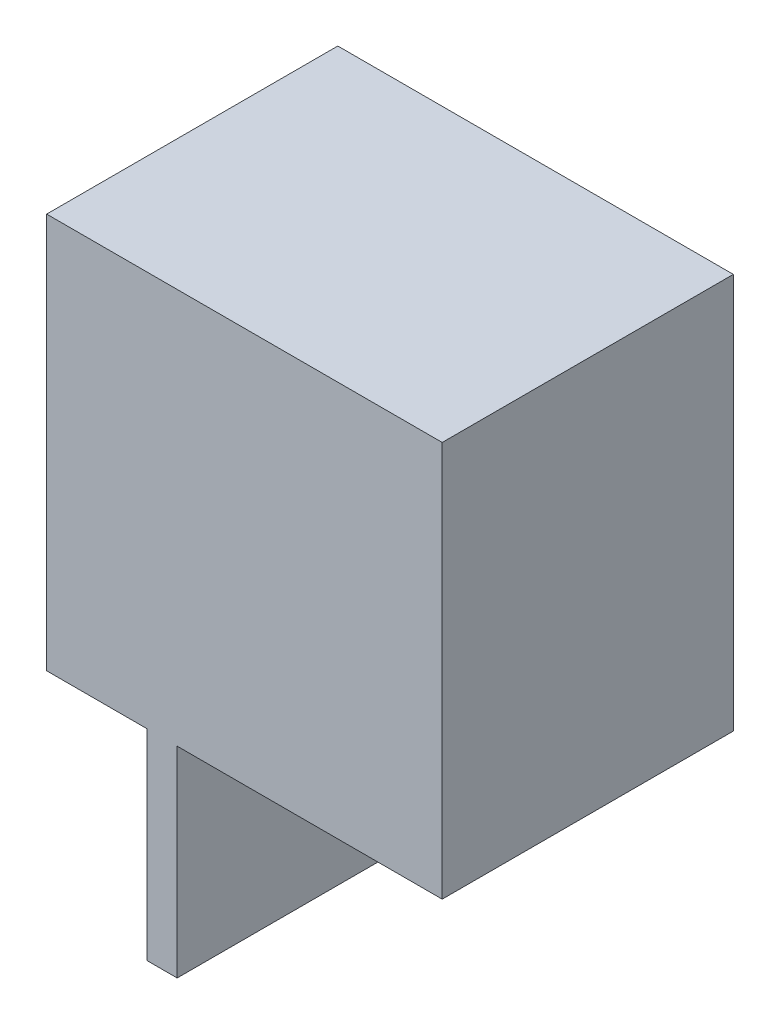
SolidWorks part; units mm, degrees
ref_plane "Front Plane" through (0, 0, 0) normal (0, 0, 1) x (1, 0, 0)
ref_plane "Top Plane" through (0, 0, 0) normal (0, 1, 0) x (1, 0, 0)
ref_plane "Right Plane" through (0, 0, 0) normal (1, 0, 0) x (0, 0, -1)
sketch "Sketch2" plane through (0, 0, 0) normal (0, 0, 1) x (1, 0, 0)
  line L1 (0, 0) -> (42.418, 0)
  line L2 (0, 0) -> (0, 42.418)
  line L3 (0, 42.418) -> (42.418, 42.418)
  line L4 (42.418, 0) -> (42.418, 42.418)
  line L5 (-3.81, 46.228) -> (46.228, 46.228)
  line L6 (-3.81, 46.228) -> (-3.81, -3.81)
  line L7 (-3.81, -3.81) -> (46.228, -3.81)
  line L8 (46.228, 46.228) -> (46.228, -3.81)
  dimension "D1" = 42.418
  dimension "D2" = 42.418
  dimension "D3" = 3.81
  dimension "D4" = 3.81
  dimension "D5" = 3.81
  dimension "D6" = 3.81
extrude "Boss-Extrude1" add sketch "Sketch2" along normal blind 34.29
sketch "Sketch4" plane through (0, 0, 34.29) normal (0, 0, 1) x (1, 0, 0)
  line L1 (-3.81, 46.228) -> (46.228, 46.228)
  line L2 (-3.81, 46.228) -> (-3.81, -3.81)
  line L3 (-3.81, -3.81) -> (46.228, -3.81)
  line L4 (46.228, 46.228) -> (46.228, -3.81)
extrude "Boss-Extrude2" add sketch "Sketch4" along normal blind 2.54
sketch "Sketch5" plane through (0, 0, 0) normal (0, 0, -1) x (-1, 0, 0)
  line L6 (3.81, -3.81) -> (-46.228, -3.81) construction
  line L7 (-12.7, -3.81) -> (-8.89, -3.81)
  line L8 (-12.7, -3.81) -> (-12.7, -29.21)
  line L9 (-12.7, -29.21) -> (-8.89, -29.21)
  line L10 (-8.89, -3.81) -> (-8.89, -29.21)
  line L11 (3.81, 46.228) -> (3.81, -3.81) construction
  dimension "D1" = 12.7
  dimension "D2" = 3.81
  dimension "D3" = 25.4
extrude "Boss-Extrude3" add sketch "Sketch5" against normal up to surface (36.83 mm away) up to face at (21.209, 21.209, 36.83)
